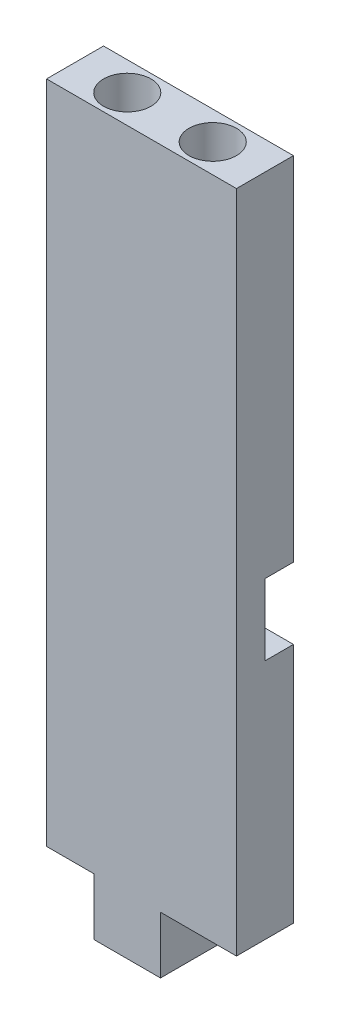
SolidWorks part; units mm, degrees
material "Plywood"
ref_plane "Plan de face" through (0, 0, 0) normal (0, 0, 1) x (1, 0, 0)
ref_plane "Plan de dessus" through (0, 0, 0) normal (0, 1, 0) x (1, 0, 0)
ref_plane "Plan de droite" through (0, 0, 0) normal (1, 0, 0) x (0, 0, -1)
sketch "Esquisse1" plane through (0, 0, 0) normal (0, 0, 1) x (1, 0, 0)
  line L1 (0, 0) -> (20, 0)
  line L2 (0, 0) -> (0, 70)
  line L3 (0, 70) -> (20, 70)
  line L4 (20, 0) -> (20, 70)
  dimension "D1" = 20
  dimension "D2" = 70
extrude "Boss.-Extru.1" add sketch "Esquisse1" along normal blind 6
sketch "Esquisse2" plane through (0, 0, 0) normal (0, 0, -1) x (-1, 0, 0)
  line L0 (0, 70) -> (0, 0) construction
  line L1 (0, 25.4246) -> (-8, 25.4246)
  line L2 (0, 25.4246) -> (0, 32.9246)
  line L3 (0, 32.9246) -> (-8, 32.9246)
  line L4 (-8, 25.4246) -> (-8, 32.9246)
  line L5 (-20, 0) -> (-20, 70) construction
  line L6 (-20, 25.4246) -> (-13, 25.4246)
  line L7 (-20, 25.4246) -> (-20, 32.9246)
  line L8 (-20, 32.9246) -> (-13, 32.9246)
  line L9 (-13, 25.4246) -> (-13, 32.9246)
  line L10 (-8, 25.4246) -> (2, 25.4246) construction
  line L11 (-8, 32.9246) -> (2, 32.9246) construction
  line L12 (-13, 32.9246) -> (-13, 25.4246) construction
  line L13 (-8, 32.9246) -> (-8, 25.4246) construction
extrude "Enlèv. mat.-Extru.1" cut sketch "Esquisse2" against normal blind 3
sketch "Esquisse3" plane through (0, 0, 0) normal (0, -1, 0) x (1, 0, 0)
  line L0 (0, 0) -> (20, 0) construction
  line L1 (12, 0) -> (5, 0)
  line L2 (12, 0) -> (12, 6)
  line L3 (12, 6) -> (5, 6)
  line L4 (5, 0) -> (5, 6)
  line L5 (0, 6) -> (20, 6) construction
extrude "Boss.-Extru.2" add sketch "Esquisse3" along normal blind 6
sketch "Esquisse4" plane through (0, 70, 0) normal (0, 1, 0) x (1, 0, 0)
  line L0 (20, 0) -> (0, 0) construction
  line L1 (0, -6) -> (0, 0) construction
  circle A0 centre (5.5, -3) radius 2.5
  dimension "D1" = 5
  dimension "D2" = 3
  dimension "D3" = 5.5
extrude "Enlèv. mat.-Extru.2" cut sketch "Esquisse4" against normal blind 10
pattern_linear "Répétition linéaire1" count 2 spacing 9 along (1, 0, 0) of "Enlèv. mat.-Extru.2"
